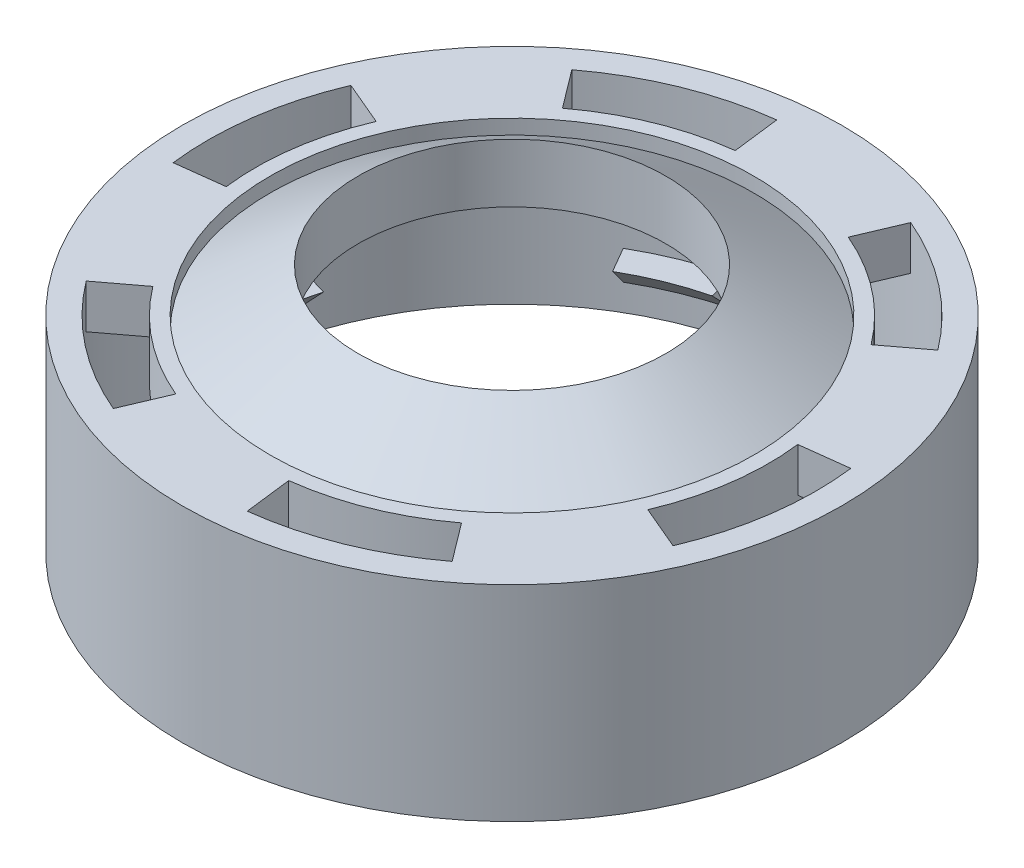
SolidWorks part; units mm, degrees
ref_plane "Frontal" through (0, 0, 0) normal (0, 0, 1) x (1, 0, 0)
ref_plane "Horizontal" through (0, 0, 0) normal (0, 1, 0) x (1, 0, 0)
ref_plane "Profile" through (0, 0, 0) normal (1, 0, 0) x (0, 0, -1)
sketch "Sketch1" plane through (0, 0, 0) normal (0, 1, 0) x (1, 0, 0)
  circle A0 centre (0, 0) radius 22.5
  circle A1 centre (0, 0) radius 20.75
extrude "Extrude1" add sketch "Sketch1" along normal blind 14
sketch "Sketch3" plane through (0, 0, 0) normal (0, 0, 1) x (1, 0, 0)
  line L0 (-20.75, 3.8) -> (-18.75, 3.8)
  line L1 (-20.75, 14) -> (-20.75, 0) construction
  line L2 (-18.75, 3.8) -> (-20.75, 1.8)
  line L3 (-20.75, 0) -> (20.75, 0) construction
  dimension "D1" = 2
  dimension "D2" = 2
  dimension "D3" = 1.8
sketch "Sketch4" plane through (0, 0, 0) normal (0, 0, 1) x (1, 0, 0)
  line L0 (-20.75, 3.8) -> (-18.75, 3.8)
  line L1 (-18.75, 3.8) -> (-20.75, 1.8)
  line L2 (-20.75, 3.8) -> (-20.75, 1.8)
revolve "Revolve6" add sketch "Sketch4" angle 16 about axis through (0, 14, 0) along (0, -1, 0)
pattern_circular "CirPattern1" count 6 over 360 about axis through (0, 0, 0) along (0, 1, 0) of "Revolve6"
ref_plane "Plane1" through (0, 10, 0) normal (0, 1, 0) x (-1, 0, 0)
sketch "Sketch5" plane through (0, 10, 0) normal (0, 1, 0) x (-1, 0, 0)
  circle A0 centre (0, 0) radius 16.5
  circle A1 centre (0, 0) radius 17.5
extrude "Extrude2" add sketch "Sketch5" along normal blind 4
ref_plane "Plane2" through (0, 13, 0) normal (0, 1, 0) x (-1, 0, 0)
sketch "Sketch6" plane through (0, 13, 0) normal (0, 1, 0) x (-1, 0, 0)
  circle A0 centre (0, 0) radius 16.5
ref_plane "Plane3" through (0, 17, 0) normal (0, 1, 0) x (-1, 0, 0)
sketch "Sketch7" plane through (0, 17, 0) normal (0, 1, 0) x (-1, 0, 0)
  circle A0 centre (0, 0) radius 10.5
loft "Loft1" add profiles "Sketch7", "Sketch6"
sketch "Sketch8" plane through (0, 17, 0) normal (0, 1, 0) x (-1, 0, 0)
  circle A0 centre (0, 0) radius 10.5
extrude "Cut-Extrude1" cut sketch "Sketch8" against normal through all
sketch "Sketch9" plane through (0, 14, 0) normal (0, 1, 0) x (-1, 0, 0)
  line L0 (-3.4046, -24.2252) -> (0, 0) construction
  line L1 (4.536, -18.193) -> (5.0199, -20.1336) construction
  line L2 (0, 0) -> (2.5288, -20.5953)
  line L3 (0, 0) -> (-8.1077, -19.1005)
  circle A0 centre (0, 0) radius 20.75 construction
  arc A1 (2.5288, -20.5953) -> (-8.1077, -19.1005) centre (0, 0) cw
  arc A2 (2.1327, -17.3696) -> (-6.8378, -16.1088) centre (0, 0) cw
  circle A3 centre (0, 0) radius 17.5 construction
  circle M2 centre (0, 0) radius 20.75
  dimension "D1" = 22
  dimension "D2" = 15
  dimension "D3" = 15
extrude "Extrude3" add sketch "Sketch9" against normal blind 3 contours L0 A2 L3 M2 | L0 A1 L2 A2
sketch "Sketch10" plane through (0, 14, 0) normal (0, 1, 0) x (-1, 0, 0)
  line L0 (-3.4046, -24.2252) -> (0, 0) construction
sketch "Sketch12" plane through (0, 0, 0) normal (0, 1, 0) x (1, 0, 0)
  line L0 (3.4046, 24.2252) -> (0, 0) construction
pattern_circular "CirPattern2" count 6 over 360 about axis through (0, 0, 0) along (0, 1, 0) of "Extrude3"
